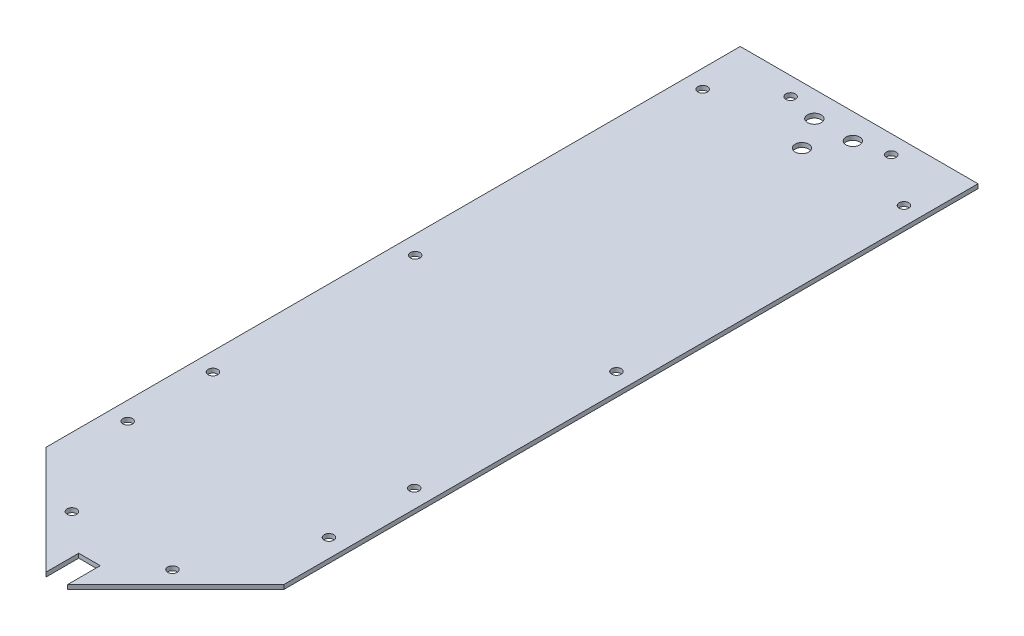
SolidWorks part; units mm, degrees
material "6061-T6 (SS)"
ref_plane "Front Plane" through (0, 0, 0) normal (0, 0, 1) x (1, 0, 0)
ref_plane "Top Plane" through (0, 0, 0) normal (0, 1, 0) x (1, 0, 0)
ref_plane "Right Plane" through (0, 0, 0) normal (1, 0, 0) x (0, 0, -1)
sketch "Sketch1" plane through (0, 0, 0) normal (0, 1, 0) x (1, 0, 0)
  line L0 (-82.7, 0) -> (82.7, 0) construction
  line L2 (7.5, 7.5) -> (82.7, 82.7)
  line L3 (82.7, 0) -> (82.7, 565.6605) construction
  line L4 (82.7, 82.7) -> (82.7, 565.6605)
  line L8 (-7.5, 7.5) -> (-82.7, 82.7)
  line L9 (-82.7, 82.7) -> (-82.7, 565.6605)
  line L10 (-82.7, 565.6605) -> (82.7, 565.6605)
  line L13 (-7.5, 30.2724) -> (7.5, 30.2724)
  line L14 (7.5, 30.2724) -> (7.5, 7.5)
  line L15 (-7.5, 30.2724) -> (-7.5, 7.5)
  point P4 (0, 0)
  point P13 (0, 30.2724)
  dimension "D1" = 165.4
  dimension "D2" = 45
  dimension "D3" = 106.3489
  dimension "D4" = 565.6605
  dimension "D5" = 15
extrude "Boss-Extrude1" add sketch "Sketch1" against normal blind 3
sketch "Sketch2" plane through (0, 0, 0) normal (0, 1, 0) x (1, 0, 0)
  line L0 (-73.0567, 82.7) -> (-7.5, 18.8862) construction
  line L1 (-82.7, 324.1803) -> (82.7, 324.1803) construction
  line L2 (-31.0839, 41.8431) -> (-31.0839, 52.896) construction
  line L3 (82.7, 82.7) -> (82.7, 565.6605) construction
  line L4 (82.7, 565.6605) -> (-82.7, 565.6605) construction
  line L5 (-73.0567, 565.6605) -> (-73.0567, 73.0567) construction
  line L8 (-82.7, 82.7) -> (-73.0567, 82.7) construction
  line L9 (0, 565.6605) -> (0, 30.2724) construction
  circle A0 centre (-73.0567, 550.1313) radius 3.325
  circle A1 centre (73.0567, 550.1313) radius 3.325
  circle A2 centre (-73.0567, 324.1803) radius 3.325
  circle A3 centre (-73.0567, 82.7) radius 3.325
  circle A4 centre (73.0567, 82.7) radius 3.325
  circle A5 centre (73.0567, 324.1803) radius 3.325
  circle A10 centre (-31.0839, 52.896) radius 3.325
  circle A11 centre (31.0839, 52.896) radius 3.325
  dimension "D1" = 6.65
  dimension "D2" = 9.6433
  dimension "D3" = 51.6161
  dimension "D4" = 82.7
  dimension "D5" = 113.7839
  dimension "D6" = 155.7567
  dimension "D7" = 165.4
  dimension "D8" = 15.5292
  dimension "D9" = 241.4803
  dimension "D10" = 482.9605
  dimension "D11" = 512.7645
  dimension "D12" = 91.487
  dimension "D13" = 492.6038
sketch "Sketch8" plane through (0, 0, 0) normal (0, 1, 0) x (1, 0, 0)
  line L0 (-82.7, 324.1803) -> (82.7, 324.1803) construction
  line L1 (-82.7, 565.6605) -> (-82.7, 82.7) construction
  line L2 (82.7, 82.7) -> (82.7, 565.6605) construction
  line L3 (82.7, 565.6605) -> (-82.7, 565.6605) construction
  line L4 (82.7, 565.6605) -> (-82.7, 565.6605)
  line L5 (0, 324.1803) -> (0, 251.1063) construction
  line L6 (0.0302, 565.6605) -> (0.0302, 17.9605) construction
  line L7 (-69.9698, 565.6605) -> (-69.9698, 87.9605) construction
  line L8 (-69.9698, 87.9605) -> (0.0302, 17.9605) construction
  line L9 (0.0302, 17.9605) -> (70.0302, 87.9605) construction
  line L10 (70.0302, 87.9605) -> (70.0302, 565.6605) construction
  line L11 (0.0302, 552.9605) -> (70.0302, 552.9605) construction
  line L12 (0.0302, 552.9605) -> (-31.6448, 552.9605) construction
  line L13 (-31.6448, 552.9605) -> (-69.9698, 552.9605) construction
  circle A0 centre (-69.9698, 326.8105) radius 3.325
  circle A1 centre (70.0302, 326.8105) radius 3.325
  circle A2 centre (-69.9698, 126.8105) radius 3.325
  circle A3 centre (-69.9698, 326.8105) radius 3.325
  circle A4 centre (-69.9698, 526.8105) radius 3.325
  circle A5 centre (70.0302, 126.8105) radius 3.325
  circle A6 centre (70.0302, 526.8105) radius 3.325
  circle A7 centre (-34.9698, 52.9605) radius 3.325
  circle A8 centre (35.0302, 52.9605) radius 3.325
  circle A9 centre (35.0302, 552.9605) radius 3.325
  circle A10 centre (-34.9698, 552.9605) radius 3.325
  circle A11 centre (-69.9698, 186.1217) radius 3.325
  circle A12 centre (70.0302, 186.1217) radius 3.325
  dimension "D1" = 6.65
  dimension "D10" = 6.65
  dimension "D2" = 12.7
  dimension "D3" = 12.6698
  dimension "D4" = 47.6698
  dimension "D5" = 38.85
  dimension "D6" = 238.85
  dimension "D7" = 438.85
  dimension "D8" = 73.074
  dimension "D9" = 178.6217
extrude "Cut-Extrude2" cut sketch "Sketch8" against normal through all both and the other way through all contours A10 | A9 | A4 | A6 | A1 | A0 | A2 | A7 | A8 | A5 | A11 | A12 region at (-69.9698, 0, -326.8105) region at (70.0302, 0, -326.8105) region at (-69.9698, 0, -126.8105) region at (-69.9698, 0, -526.8105) region at (70.0302, 0, -126.8105) region at (70.0302, 0, -526.8105) region at (-34.9698, 0, -52.9605) region at (35.0302, 0, -52.9605) region at (35.0302, 0, -552.9605) region at (-34.9698, 0, -552.9605)
sketch "Sketch9" plane through (0, 0, 0) normal (0, 1, 0) x (1, 0, 0)
  line L0 (0, 565.6605) -> (0, 512.6605) construction
  line L2 (12.8474, 512.6605) -> (12.8474, 525.9105) construction
  line L3 (0, 525.9105) -> (13.4, 525.9105) construction
  line L4 (13.4, 525.9105) -> (13.4, 547.9105) construction
  line L6 (82.7, 82.7) -> (82.7, 565.6605) construction
  circle A0 centre (0, 525.9105) radius 4.75
  circle A1 centre (13.4, 547.9105) radius 4.75
  circle A2 centre (-13.4, 547.9105) radius 4.75
  dimension "D3" = 69.8526
  dimension "D4" = 82.7
  dimension "D1" = 9.5
  dimension "D2" = 69.3
  dimension "D5" = 96.1
  dimension "D6" = 17.75
  dimension "D7" = 39.75
  dimension "D8" = 53
extrude "Cut-Extrude3" cut sketch "Sketch9" against normal through all both and the other way through all
